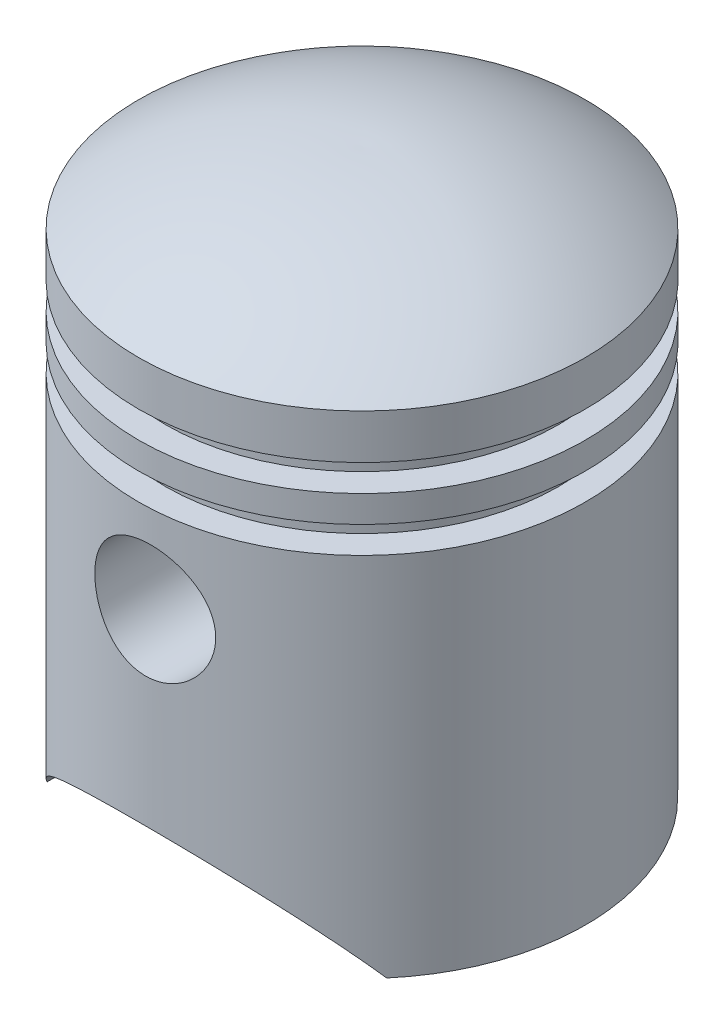
SolidWorks part; units mm, degrees
ref_plane "Ön Düzlem" through (0, 0, 0) normal (0, 0, 1) x (1, 0, 0)
ref_plane "Üst Düzlem" through (0, 0, 0) normal (0, 1, 0) x (1, 0, 0)
ref_plane "Sağ Düzlem" through (0, 0, 0) normal (1, 0, 0) x (0, 0, -1)
sketch "Çizim1" plane through (0, 0, 0) normal (0, 0, 1) x (1, 0, 0)
  line L0 (-16.6736, -12.8566) -> (-16.6736, 28.1434)
  line L1 (-16.6736, 28.1434) -> (-13.6736, 28.1434)
  line L2 (-13.6736, 28.1434) -> (-13.6736, 31.1434)
  line L3 (-13.6736, 31.1434) -> (-16.6736, 31.1434)
  line L4 (-16.6736, 31.1434) -> (-16.6736, 34.1434)
  line L5 (-16.6736, 34.1434) -> (-13.6736, 34.1434)
  line L6 (-13.6736, 34.1434) -> (-13.6736, 37.1434)
  line L7 (-13.6736, 37.1434) -> (-16.6736, 37.1434)
  line L8 (-16.6736, 37.1434) -> (-16.6736, 42.1434)
  line L9 (-14.6736, -12.8566) -> (-14.6736, 26.1434)
  line L10 (-14.6736, 26.1434) -> (-11.6736, 26.1434)
  line L11 (-11.6736, 39.1434) -> (-11.6736, 26.1434)
  line L12 (8.3264, 50.1434) -> (8.3264, -17.7111) construction
  line L16 (-11.6736, 39.1434) -> (-14.6736, 39.1434)
  line L17 (-14.6736, 39.1434) -> (-14.6736, 41.1279)
  line L18 (8.2772, 48.144) -> (8.3264, 48.144)
  line L19 (8.3264, 48.144) -> (8.3264, 50.1434)
  line L20 (-16.6736, -12.8566) -> (-14.6736, -12.8566)
  line L22 (-11.6736, 32.6434) -> (-11.6736, 39.1434) construction
  line L23 (-11.6736, 32.6434) -> (-11.6736, 32.6434) construction
  line L24 (-11.6736, 32.6434) -> (-11.6736, 32.6434) construction
  line L25 (-11.6736, 32.6434) -> (-11.6736, 32.6434) construction
  line L26 (-11.6736, 26.1434) -> (-11.6736, 32.6434) construction
  arc A0 (-16.6736, 42.1434) -> (8.3264, 50.1434) centre (7.3425, 10.1555) cw
  arc A1 (-14.6736, 41.1279) -> (8.2772, 48.144) centre (7.3425, 10.1555) cw
revolve "Döndür39" add sketch "Çizim1" angle 360 about L12
sketch "Çizim3" plane through (0, 0, 0) normal (0, 0, 1) x (1, 0, 0)
  line L1 (-16.6736, -12.8566) -> (33.3264, -12.8566) construction
  line L2 (-10.6736, -12.8566) -> (27.3264, -12.8566)
  arc A0 (27.3264, -12.8566) -> (-10.6736, -12.8566) centre (8.3264, -25.9066) ccw
extrude "Kes-Ekstrüzyon1" cut sketch "Çizim3" against normal blind 25 and the other way blind 25
sketch "Çizim4" plane through (0, 0, 0) normal (0, 0, 1) x (1, 0, 0)
  line L0 (9.3103, 50.1555) -> (9.3103, -14.3467) construction
  arc A0 (33.3264, 42.1434) -> (9.3103, 50.1555) centre (9.3103, 10.1555) ccw construction
  circle A1 centre (9.3103, 18.1555) radius 6.5
extrude "Kes-Ekstrüzyon2" cut sketch "Çizim4" against normal blind 25 and the other way blind 25
sketch "Çizim5" plane through (0, 0, 0) normal (0, 0, 1) x (1, 0, 0)
  circle A0 centre (9.3103, 18.1555) radius 6.5
  circle A1 centre (9.3103, 18.1555) radius 7.5
extrude "Yükseklik-Ekstrüzyon1" add sketch "Çizim5" against normal up to surface (9.7484 mm away) from offset 12 up to face at (15.6914, 16.918, -21.7889) offset against normal yes
mirror "Aynalama1" about plane through (0, 0, 0) normal (0, 0, 1) of "Yükseklik-Ekstrüzyon1"
